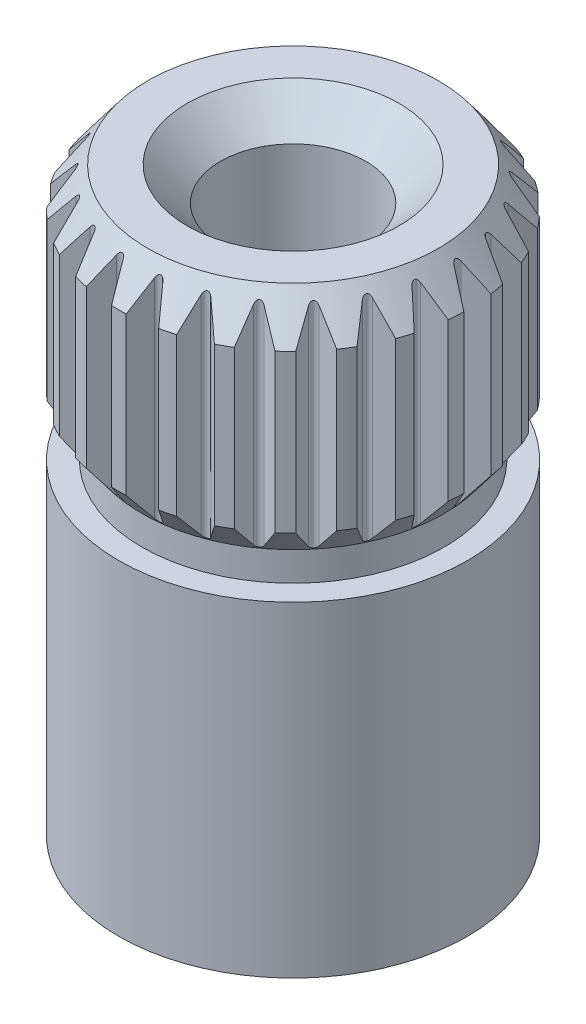
SolidWorks part; units mm, degrees
material "Laiton"
ref_plane "Plan de face" through (0, 0, 0) normal (0, 0, 1) x (1, 0, 0)
ref_plane "Plan de dessus" through (0, 0, 0) normal (0, 1, 0) x (1, 0, 0)
ref_plane "Plan de droite" through (0, 0, 0) normal (1, 0, 0) x (0, 0, -1)
ref_axis "Axe1" through (0, 0, 0) along (0, 1, 0)
sketch "Esquisse5" plane through (0, 0, 0) normal (0, 0, 1) x (1, 0, 0)
  line L0 (0, 0) -> (0, 44.2) construction
  line L1 (-2.5, 44.2) -> (0, 44.2)
  line L2 (-3, 43.5365) -> (-3, 40.8308)
  line L3 (-2.5, 44.2) -> (-3, 43.5365)
  line L4 (-3, 40.8308) -> (-2.6, 40.3)
  line L5 (-2.6, 40.3) -> (-2.6, 39.8)
  line L6 (0, 44.2) -> (2.5, 44.2) construction
  line L7 (2.5, 44.2) -> (3, 43.5365) construction
  line L8 (3, 43.5365) -> (3, 40.8308) construction
  line L9 (-3, 34.2) -> (0, 34.2)
  line L10 (0, 44.2) -> (0, 34.2)
  line L11 (-2.6, 39.8) -> (-3, 39.8)
  line L12 (-3, 39.8) -> (-3, 34.2)
  dimension "D1" = 44.2
  dimension "D2" = 6
  dimension "D3" = 5
  dimension "D4" = 5.2
  dimension "D5" = 3.9
  dimension "D6" = 37
  dimension "D7" = 37
  dimension "D8" = 4.4
  dimension "D9" = 10
revolve "Révolution1" add sketch "Esquisse5" angle 360 about L0
sketch "Esquisse1" plane through (0, 44.2, 0) normal (0, 1, 0) x (1, 0, 0)
  line L0 (0, 0) -> (0, 3) construction
  line L1 (-0.25, 2.9896) -> (-0.0636, 2.6667)
  line L2 (0.25, 2.9896) -> (0.0636, 2.6667)
  circle A0 centre (0, 0) radius 3
  circle A1 centre (0, 0) radius 1.825
  circle A2 centre (0, 0) radius 2.5
  circle A3 centre (0, 0) radius 1.5 construction
  circle A4 centre (0, 0) radius 1.2294
  arc A5 (-0.0636, 2.6667) -> (0.0636, 2.6667) centre (0, 2.7034) ccw
  dimension "D1" = 6
  dimension "D2" = 5
  dimension "D3" = 3.65
  dimension "D4" = 3
  dimension "D5" = 2.4588
  dimension "D6" = 60
  dimension "D7" = 0.37
  dimension "D8" = 0.5
sketch "Esquisse3" plane through (0, 44.2, 0) normal (0, 1, 0) x (1, 0, 0)
  line L0 (0.25, 2.9896) -> (0.0636, 2.6667) construction
  line L1 (-0.25, 2.9896) -> (-0.0636, 2.6667) construction
  line L2 (0.25, 2.9896) -> (0.0636, 2.6667)
  line L3 (-0.25, 2.9896) -> (-0.0636, 2.6667)
  arc A0 (-0.0636, 2.6667) -> (0.0636, 2.6667) centre (0, 2.7034) ccw construction
  arc A1 (-0.0636, 2.6667) -> (0.0636, 2.6667) centre (0, 2.7034) ccw
  arc A2 (0.25, 2.9896) -> (-0.25, 2.9896) centre (0, 0) ccw
  circle A3 centre (0, 0) radius 3 construction
extrude "Enlèv. mat.-Extru.2" cut sketch "Esquisse3" against normal up to next
pattern_circular "Répétition circulaire2" count 25 over 360 about axis through (0, 0, 0) along (0, 1, 0) of "Enlèv. mat.-Extru.2"
hole_wizard "Trou taraudé M31" positions "Esquisse8" profile "Esquisse7" tap size "M3" standard "ISO"
sketch "Esquisse8" plane through (0, 44.2, 0) normal (0, 1, 0) x (1, 0, 0)
  point P0 (0, 0)
sketch "Esquisse7" plane through (0, 44.2, 0) normal (1, 0, 0) x (0, 0, 1)
  line L0 (0, 0) -> (0, 9.7511)
  line L1 (0, 9.7511) -> (1.25, 9)
  line L2 (1.25, 9) -> (1.25, 0)
  line L5 (1.25, 0) -> (0, 0)
  line L10 (0, 9.7511) -> (-1.25, 9) construction
  line L11 (0, -6.35) -> (0, 107.95) construction
  dimension "Diamètre du trou pour taraudage" = 2.5
  dimension "Profondeur du trou pour taraudage" = 9
  dimension "Angle de pointe" = 118
cosmetic thread "Filetage de perçage1" parameters "D1"=6.5, "D2"=3
sketch "Esquisse9" plane through (0, 0, 0) normal (0, 0, 1) x (1, 0, 0)
  line L0 (1.825, 44.2) -> (0, 42.375)
  line L2 (1.825, 44.2) -> (-1.825, 44.2) construction
  line L3 (1.825, 44.2) -> (0, 44.2)
  line L4 (0, 44.2) -> (0, 42.375)
  line L5 (0, 45.0237) -> (0, 44.2) construction
  dimension "D1" = 45
revolve "Enlèvement de matière-Révolution1" cut sketch "Esquisse9" angle 360 about L5
